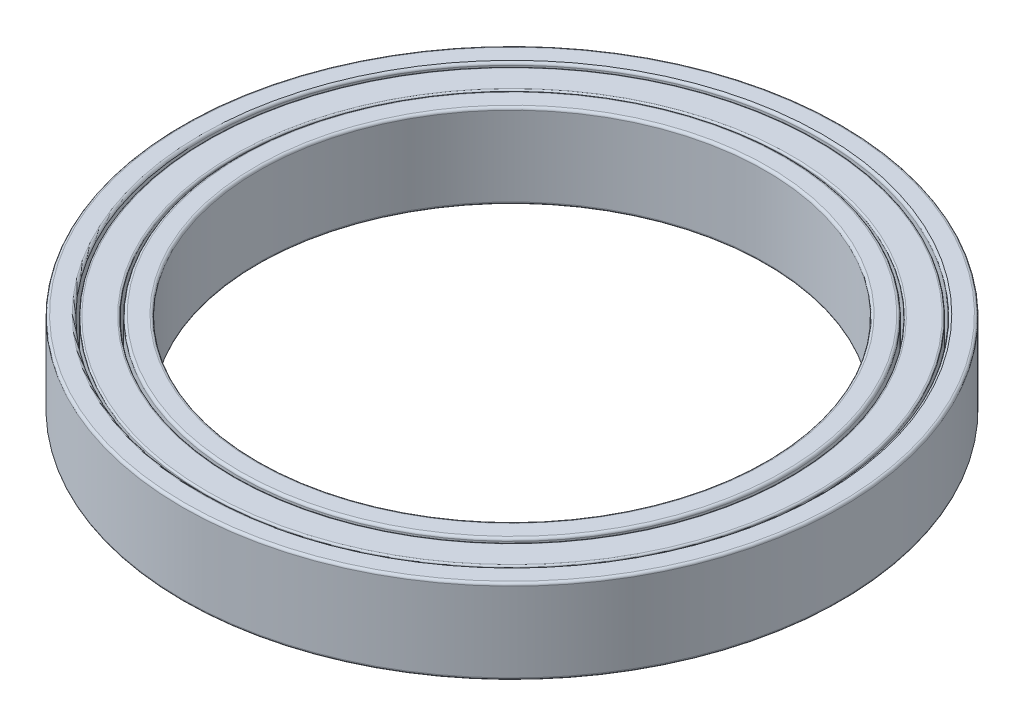
SolidWorks part; units mm, degrees
ref_plane "Front Plane" through (0, 0, 0) normal (0, 0, 1) x (1, 0, 0)
ref_plane "Top Plane" through (0, 0, 0) normal (0, 1, 0) x (1, 0, 0)
ref_plane "Right Plane" through (0, 0, 0) normal (1, 0, 0) x (0, 0, -1)
sketch "Sketch1" plane through (0, 0, 0) normal (0, 1, 0) x (1, 0, 0)
  circle A0 centre (0, 0) radius 30
  circle A1 centre (0, 0) radius 39 construction
  circle A2 centre (0, 0) radius 36.5 construction
  circle A3 centre (0, 0) radius 32.5
  dimension "D1" = 60
  dimension "D2" = 78
  dimension "D3" = 2.5
  dimension "D4" = 2.5
extrude "Boss-Extrude1" add sketch "Sketch1" along normal blind 10
sketch "Sketch2" plane through (0, 0, 0) normal (0, 1, 0) x (1, 0, 0)
  circle A0 centre (0, 0) radius 39 construction
  circle A1 centre (0, 0) radius 36.5 construction
  circle A2 centre (0, 0) radius 39
  circle A3 centre (0, 0) radius 36.5
extrude "Boss-Extrude2" add sketch "Sketch2" along normal up to surface (10 mm away) separate body up to face at (0, 10, 32.5)
sketch "Sketch3" plane through (0, 10, 0) normal (0, 1, 0) x (1, 0, 0)
  circle A4 centre (0, 0) radius 32.8
  circle A5 centre (0, 0) radius 32.8
  circle A7 centre (0, 0) radius 36.2
  circle A8 centre (0, 0) radius 36.2
  dimension "D1" = 0.3
  dimension "D2" = 0.3
extrude "Boss-Extrude3" add sketch "Sketch3" against normal offset from surface (9.6 mm away) 0.2 from offset 0.2 separate body up to face at (0, 0, 39) offset against normal yes
fillet "Fillet1" radius 0.3 4 edges at (0, 0, 39) (0, 10, 39) (0, 0, 36.5) (0, 10, 36.5)
fillet "Fillet2" radius 0.3 4 edges at (0, 0, 30) (0, 0, 32.5) (0, 10, 30) (0, 10, 32.5)
fillet "Fillet3" radius 0.2 4 edges at (0, 0.2, 32.8) (0, 0.2, 36.2) (0, 9.8, 36.2) (0, 9.8, 32.8)
